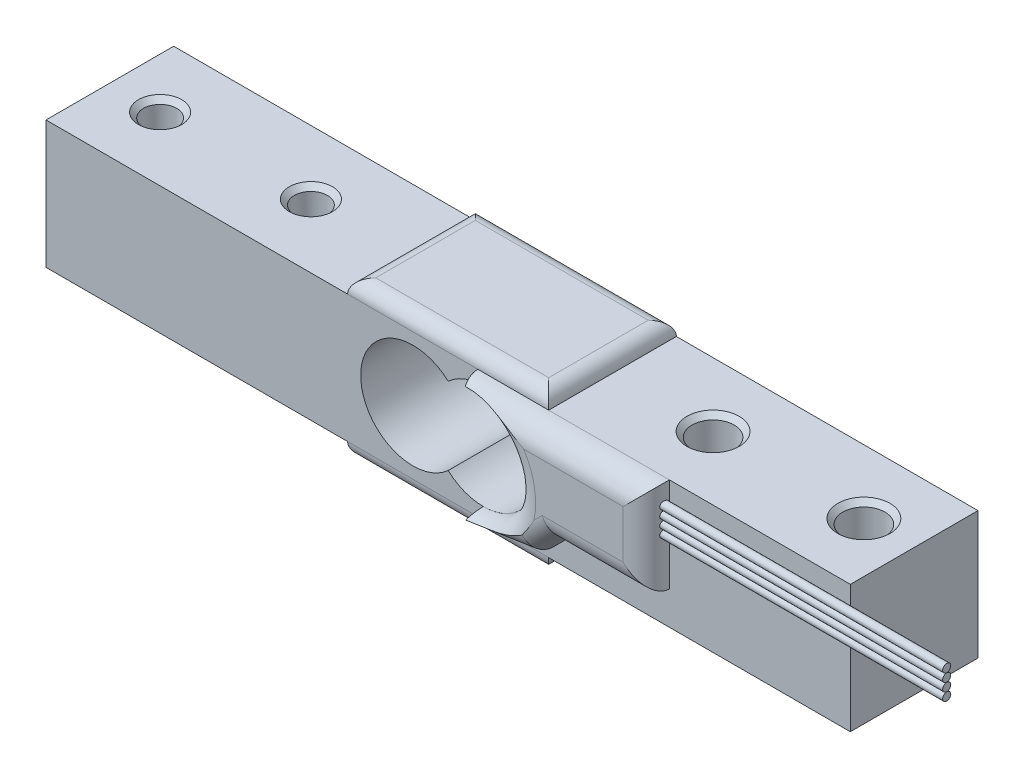
SolidWorks part; units mm, degrees
ref_plane "前视基准面" through (0, 0, 0) normal (0, 0, 1) x (1, 0, 0)
ref_plane "上视基准面" through (0, 0, 0) normal (0, 1, 0) x (1, 0, 0)
ref_plane "右视基准面" through (0, 0, 0) normal (1, 0, 0) x (0, 0, -1)
sketch "草图1" plane through (0, 0, 0) normal (0, 0, 1) x (1, 0, 0)
  line L1 (-40, 6.35) -> (40, 6.35)
  line L2 (-40, 6.35) -> (-40, -6.35)
  line L3 (-40, -6.35) -> (40, -6.35)
  line L4 (40, 6.35) -> (40, -6.35)
  line L5 (-40, 6.35) -> (40, -6.35) construction
  line L6 (-40, -6.35) -> (40, 6.35) construction
  arc A0 (0, 3.8458) -> (0, -3.8458) centre (-3.5, 0) ccw
  arc A2 (0, -3.8458) -> (0, 3.8458) centre (3.5, 0) ccw
  point P0 (0, 0)
  dimension "D1" = 12.7
  dimension "D2" = 80
extrude "凸台-拉伸1" add sketch "草图1" along normal mid plane 12.7
sketch "草图3" plane through (0, 6.35, 0) normal (0, 1, 0) x (1, 0, 0)
  point P0 (-35, 0)
  point P4 (0, 0)
  point P6 (-20, 0)
  point P7 (20, 0)
  point P8 (35, 0)
hole_wizard "M4 螺纹孔1" positions "3D草图1" profile "草图4" tap size "M4" standard "GB" end condition through all
sketch3d "3D草图1"
  point P0 (-35, 6.35, 0)
  point P3 (-20, 6.35, 0)
sketch "草图4" plane through (-35, 6.35, 0) normal (1, 0, 0) x (0, 0, 1)
  line L0 (0, 0) -> (0, 12.7)
  line L1 (0, 12.7) -> (1.65, 12.7)
  line L2 (1.65, 12.7) -> (1.65, 0)
  line L5 (1.65, 0) -> (0, 0)
  line L11 (0, -6.35) -> (0, 107.95) construction
  dimension "通孔螺纹孔钻头直径" = 3.3
  dimension "通孔螺纹孔钻头深度" = 12.7
cosmetic thread "孔螺蚊线1" parameters "D2"=4
cosmetic thread "孔螺蚊线2" parameters "D2"=4
hole_wizard "M5 Tapped Hole1" positions "3D草图2" profile "草图5" tap size "M5" standard "GB" end condition through all
sketch3d "3D草图2"
  point P0 (20, 6.35, 0)
  point P3 (35, 6.35, 0)
sketch "草图5" plane through (20, 6.35, 0) normal (1, 0, 0) x (0, 0, 1)
  line L0 (0, 0) -> (0, 12.7)
  line L1 (0, 12.7) -> (2.1, 12.7)
  line L2 (2.1, 12.7) -> (2.1, 0)
  line L5 (2.1, 0) -> (0, 0)
  line L11 (0, -6.35) -> (0, 107.95) construction
  dimension "通孔螺纹孔钻头直径" = 4.2
  dimension "通孔螺纹孔钻头深度" = 12.7
cosmetic thread "孔螺蚊线3" parameters "D2"=5
cosmetic thread "孔螺蚊线4" parameters "D2"=5
chamfer "倒角1" distance 0.5 angle 45 8 edges at (-35, -6.35, 1.65) (-20, -6.35, 1.65) (35, -6.35, 2.1) (20, -6.35, 2.1) (35, 6.35, 2.1) (20, 6.35, 2.1) (-20, 6.35, 1.65) (-35, 6.35, 1.65)
sketch "草图2" plane through (0, 0, 0) normal (0, 0, 1) x (1, 0, 0)
  line L0 (40, 6.35) -> (-40, 6.35) construction
  line L1 (-10, 7.75) -> (10, 7.75)
  line L2 (-10, 7.75) -> (-10, 6.35)
  line L3 (-10, -7.75) -> (10, -7.75)
  line L4 (10, 7.75) -> (10, 6.35)
  line L5 (-10, 7.75) -> (-8.1935, 6.35) construction
  line L6 (-10, -7.75) -> (-8.1935, -6.35) construction
  line L7 (-10, 6.35) -> (10, 6.35)
  line L9 (-10, -6.35) -> (10, -6.35)
  line L13 (-10, -6.35) -> (-10, -7.75)
  line L14 (8.1935, -6.35) -> (10, -7.75) construction
  line L15 (8.1935, 6.35) -> (10, 7.75) construction
  line L17 (10, -6.35) -> (10, -7.75)
  point P0 (0, 0)
  point P5 (0, 0)
  dimension "D1" = 0
  dimension "D2" = 20
  dimension "D3" = 1.4
extrude "凸台-拉伸2" add sketch "草图2" along normal mid plane 12.7 separate body
fillet "圆角1" radius 1.4 4 edges at (10, 7.75, 0) (0, 7.75, 6.35) (-10, 7.75, 0) (0, 7.75, -6.35)
fillet "圆角2" radius 1.4 4 edges at (-10, -7.75, 0) (0, -7.75, 6.35) (10, -7.75, 0) (0, -7.75, -6.35)
sketch "草图6" plane through (0, 0, 6.35) normal (0, 0, 1) x (1, 0, 0)
  line L0 (3.5, 5.2) -> (2.947, 6.35)
  line L1 (-10, 6.35) -> (10, 6.35) construction
  line L2 (3.5, -5.2) -> (2.947, -6.35)
  line L3 (10, -6.35) -> (-10, -6.35) construction
  line L4 (2.947, 6.35) -> (22, 6.35)
  line L5 (22, 6.35) -> (22, -3.05)
  line L6 (22, -3.05) -> (12.6, -3.05)
  line L7 (12.6, -3.05) -> (10.45, -5.2)
  line L8 (10.45, -5.2) -> (2.947, -6.35)
  arc A0 (3.5, -5.2) -> (3.5, 5.2) centre (3.5, 0) ccw
extrude "凸台-拉伸3" add sketch "草图6" along normal blind 2.3 separate body
fillet "圆角3" radius 2.3 6 edges at (12.4735, 6.35, 8.65) (22, 1.65, 8.65) (17.3, -3.05, 8.65) (11.525, -4.125, 8.65) (8.7, 0, 8.65) (6.6985, -5.775, 8.65)
ref_plane "基准面1" through (20, 0, 0) normal (1, 0, 0) x (0, 0, -1)
sketch "草图7" plane through (20, 0, 0) normal (1, 0, 0) x (0, 0, -1)
  circle A0 centre (-6.76, 4.35) radius 0.4
  circle A1 centre (-6.76, 3.53) radius 0.4
  circle A2 centre (-6.76, 2.71) radius 0.4
  circle A3 centre (-6.76, 1.89) radius 0.4
extrude "凸台-拉伸4" add sketch "草图7" along normal blind 30
